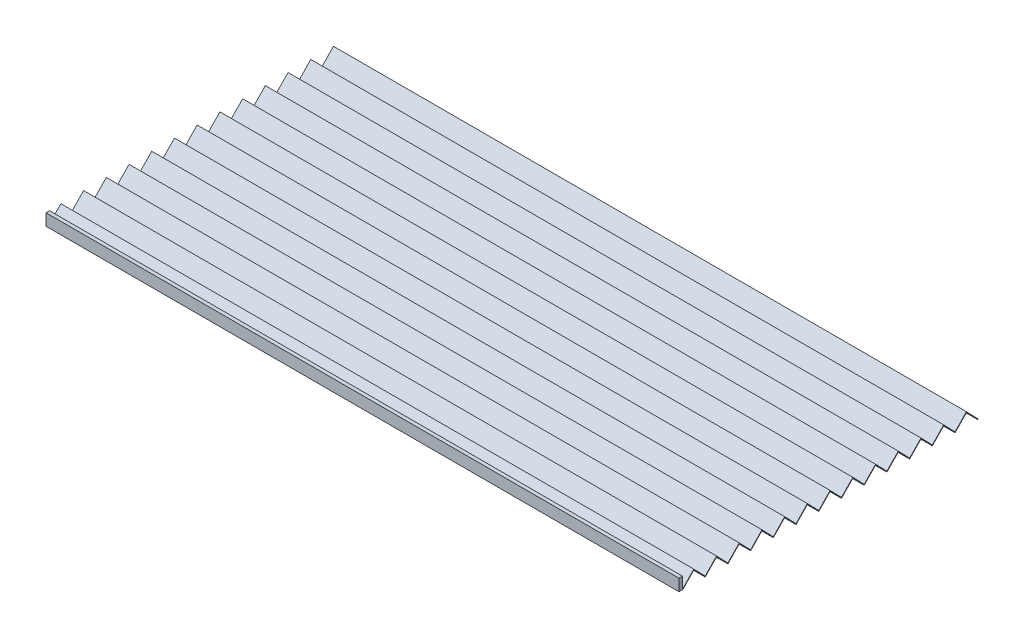
SolidWorks part; units mm, degrees
ref_plane "Front Plane" through (0, 0, 0) normal (0, 0, 1) x (1, 0, 0)
ref_plane "Top Plane" through (0, 0, 0) normal (0, 1, 0) x (1, 0, 0)
ref_plane "Right Plane" through (0, 0, 0) normal (1, 0, 0) x (0, 0, -1)
sketch "Sketch2" plane through (0, 0, 0) normal (0, 0, 1) x (1, 0, 0)
  line L1 (-270, 10) -> (270, 10)
  line L2 (-270, 10) -> (-270, 0)
  line L3 (-270, 0) -> (270, 0)
  line L4 (270, 10) -> (270, 0)
  point P4 (0, 0)
  dimension "D1" = 10
  dimension "D2" = 540
extrude "Boss-Extrude1" add sketch "Sketch2" along normal blind 3
sketch "Sketch3" plane through (270, 0, 0) normal (1, 0, 0) x (0, 0, -1)
  line L0 (0, 10) -> (251.9319, 10) construction
  line L1 (0, 0) -> (251.9319, 0) construction
  line L3 (0, 0) -> (9.6897, 10)
  line L4 (9.6897, 10) -> (19.3794, 0)
  line L5 (19.3794, 0) -> (29.0691, 10)
  line L6 (29.0691, 10) -> (38.7588, 0)
  line L7 (38.7588, 0) -> (48.4484, 10)
  line L8 (48.4484, 10) -> (58.1381, 0)
  line L9 (58.1381, 0) -> (67.8278, 10)
  line L10 (67.8278, 10) -> (77.5175, 0)
  line L11 (77.5175, 0) -> (87.2072, 10)
  line L12 (87.2072, 10) -> (96.8969, 0)
  line L13 (96.8969, 0) -> (106.5866, 10)
  line L14 (106.5866, 10) -> (116.2763, 0)
  line L15 (116.2763, 0) -> (125.9659, 10)
  line L16 (125.9659, 10) -> (135.6556, 0)
  line L17 (135.6556, 0) -> (145.3453, 10)
  line L18 (145.3453, 10) -> (155.035, 0)
  line L20 (155.035, 0) -> (164.7247, 10)
  line L21 (164.7247, 10) -> (174.4144, 0)
  line L22 (174.4144, 0) -> (184.1041, 10)
  line L23 (184.1041, 10) -> (193.7938, 0)
  line L24 (193.7938, 0) -> (203.4834, 10)
  line L25 (203.4834, 10) -> (213.1731, 0)
  line L26 (213.1731, 0) -> (222.8628, 10)
  line L27 (222.8628, 10) -> (232.5525, 0)
  line L28 (232.5525, 0) -> (242.2422, 10)
  line L29 (242.2422, 10) -> (251.9319, 0)
  line L30 (251.9319, 10) -> (251.9319, 0) construction
  line L32 (251.9319, 10) -> (251.9319, 0) construction
extrude "Extrude-Thin1" add sketch "Sketch3" against normal through all thin thin type mid plane wall 0.5
